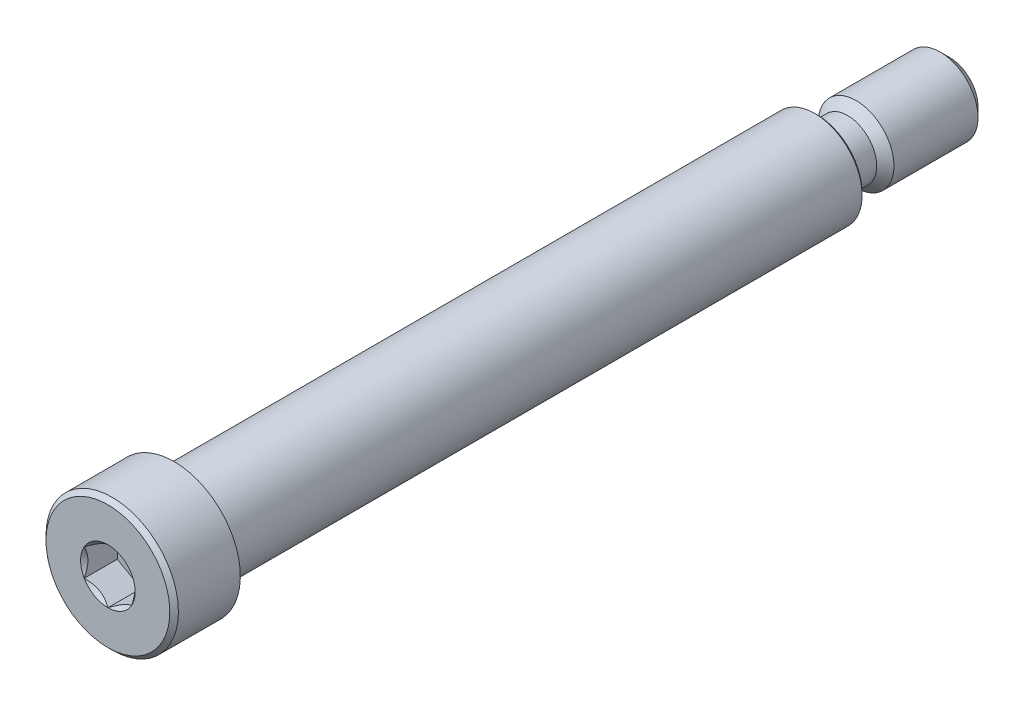
SolidWorks part; units mm, degrees
material "Cast Alloy Steel"
ref_plane "Front" through (0, 0, 0) normal (0, 0, 1) x (1, 0, 0)
ref_plane "Top" through (0, 0, 0) normal (0, 1, 0) x (1, 0, 0)
ref_plane "Right" through (0, 0, 0) normal (1, 0, 0) x (0, 0, -1)
sketch "Sketch1" plane through (0, 0, 0) normal (1, 0, 0) x (0, 0, -1)
  line L0 (0, 5.5562) -> (5.5562, 5.5562)
  line L1 (5.5562, 5.5562) -> (5.5562, 3.9687)
  line L2 (5.5562, 3.9687) -> (59.5313, 3.9687)
  line L3 (59.5313, 3.9687) -> (59.5312, 3.175)
  line L4 (59.5312, 3.175) -> (70.6438, 3.175)
  line L5 (70.6438, 3.175) -> (70.6437, 0)
  line L6 (70.6437, 0) -> (0, 0)
  line L7 (0, 0) -> (0, 5.5562)
  line L8 (0, 5.5562) -> (0, -5.5563) construction
  line L9 (70.6438, 3.175) -> (70.6437, -3.175) construction
  line L10 (59.5313, 3.9687) -> (59.5313, -3.9688) construction
  line L11 (70.6437, -3.175) -> (68.966, -3.175) construction
  line L12 (32.5437, 0) -> (32.5437, 3.9687) construction
  point P8 (68.7387, -3.175)
  point P12 (59.5312, 0)
  point P17 (10.9538, 3.9687)
  point P18 (32.5437, 0)
  point P19 (32.5437, 3.9687)
  point P20 (54.1337, 3.9687)
  point P21 (54.1337, -3.9688)
  point P22 (10.9538, -3.9688)
  dimension "Head Dia" = 11.1125
  dimension "Head Ht" = 5.5562
  dimension "Thread Lg" = 11.1125
  dimension "Thread Dia" = 6.35
  dimension "Shoulder Dia" = 7.9375
  dimension "Shoulder Lg" = 53.975
  dimension "D1" = 1.905
  dimension "D2" = 1.6778
  dimension "D3" = 26.9875
  dimension "D4" = 5.3975
revolve "Revolve1" add sketch "Sketch1" angle 360 mid plane about L6
ref_plane "Plane1" through (0, 0, -70.6437) normal (0, 0, 1) x (1, 0, 0)
sketch "Sketch3" [suppressed] plane through (0, 0, -70.6437) normal (0, 0, 1) x (1, 0, 0)
  circle A0 centre (0, 0) radius 3.175
sketch "Sketch5" plane through (0, 0, 0) normal (1, 0, 0) x (0, 0, -1)
  line L0 (59.5313, 3.9687) -> (63.5889, 3.9687)
  line L1 (63.5889, 3.9687) -> (62.0713, 2.4511)
  line L2 (62.0713, 2.4511) -> (60.2552, 2.4511)
  line L3 (59.5313, 3.9687) -> (59.5313, 3.175)
  line L5 (59.5312, 3.175) -> (70.6438, 3.175) construction
  line L6 (70.6437, 0) -> (62.0713, 0) construction
  line L7 (66.3575, 0) -> (66.3575, -3.175) construction
  arc A0 (59.5313, 3.175) -> (60.2552, 2.4511) centre (60.2552, 3.175) ccw
  dimension "D1" = 45
  dimension "CADB" = 2.54
  dimension "CADA" = 4.9022
revolve "Cut-Revolve1" cut sketch "Sketch5" angle 360 mid plane about L6
chamfer "Chamfer1" distance 0.7937 angle 45 1 edges at (0, 3.175, -70.6438)
chamfer "Chamfer2" distance 0.3612 angle 45 1 edges at (0, 5.5562, 0)
chamfer "Chamfer3" distance 0.2032 angle 45 1 edges at (0, 3.9687, -59.5313)
sketch "Sketch10" plane through (0, 0, 0) normal (1, 0, 0) x (0, 0, -1)
  line L0 (0.3612, 0) -> (5.1951, 0) construction
  line L1 (0.3612, -5.5562) -> (0.3612, 5.5562) construction
  line L3 (0.3612, 0) -> (0, 0) construction
  line L4 (5.1951, 0) -> (5.5562, 0) construction
  line L5 (5.5562, -5.5562) -> (5.5563, 5.5562) construction
  point P6 (2.7781, 0)
  dimension "D1" = 4.8339
ref_plane "Plane2" through (0, 0, -2.7781) normal (0, 0, 1) x (1, 0, 0)
sketch "Sketch11" plane through (0, 0, -2.7781) normal (0, 0, 1) x (1, 0, 0)
  line L0 (0, 5.2673) -> (0, 5.5562) construction
  line L1 (0, 5.2673) -> (0.1668, 5.5562)
  line L2 (0, 5.2673) -> (-0.1668, 5.5562)
  line L3 (-0.1668, 5.5562) -> (0.1668, 5.5562)
  line L4 (0, 0) -> (-0.1668, 5.5562) construction
  line L5 (0.1668, 5.5562) -> (0, 0) construction
  circle A1 centre (0, 0) radius 5.5562 construction
  circle A2 centre (0, 0) radius 5.2673 construction
  circle A3 centre (0, 0) radius 5.1951 construction
  point P3 (0, 0.0018)
  point P8 (2.3908, 0.7309)
  dimension "D1" = 0.2889
  dimension "D2" = 3.439
extrude "Cut-Extrude5" [suppressed] cut sketch "Sketch11" against normal mid plane 4.5922
pattern_circular "CirPattern1" [suppressed] count 99 over 360 of bodies 119
sketch "Sketch8" plane through (0, 0, 0) normal (0, 0, 1) x (1, 0, 0)
  line L1 (1.9844, 1.1457) -> (0, 2.2914)
  line L2 (0, 2.2914) -> (-1.9844, 1.1457)
  line L3 (-1.9844, 1.1457) -> (-1.9844, -1.1457)
  line L4 (-1.9844, -1.1457) -> (0, -2.2914)
  line L5 (0, -2.2914) -> (1.9844, -1.1457)
  line L6 (1.9844, -1.1457) -> (1.9844, 1.1457)
  circle A0 centre (0, 0) radius 1.9844 construction
  dimension "Hex" = 3.9688
extrude "Cut-Extrude2" cut sketch "Sketch8" against normal blind 2.7781
sketch "Sketch9" plane through (0, 0, 0) normal (0, 0, 1) x (1, 0, 0)
  circle A0 centre (0, 0) radius 2.2914
extrude "Cut-Extrude4" cut sketch "Sketch9" against normal blind 2.7781 draft 45
sketch "Front Sketch" plane through (0, 0, 0) normal (0, 0, 1) x (1, 0, 0)
  line L0 (1.9844, -1.1457) -> (1.9844, 1.1457) construction
  line L1 (-1.9844, 1.1457) -> (-1.9844, -1.1457) construction
  circle A0 centre (0, 0) radius 5.5562 construction
  point P4 (-1.9844, 0)
  point P5 (1.9844, 0)
  point P6 (5.5562, 0)
  point P9 (-5.5562, 0)
ref_plane "Contact Plane 1" [suppressed] through (0, 0, -5.5562) normal (0, 0, -1) x (-1, 0, 0)
ref_axis "Center Axis 1" [suppressed] through (0, 0, -70.6437) along (0, 0, 1)
curve "Helix/Spiral1" [suppressed] pitch 1.27 height 12.3825 turns 9.75
sketch "Sketch4" [suppressed] plane through (0, 0, 0) normal (1, 0, 0) x (0, 0, -1)
  line L0 (70.5644, 3.3125) -> (71.8344, 3.3125) construction
  line L1 (71.8344, 3.3125) -> (71.1994, 2.2126) construction
  line L3 (71.1994, 2.2126) -> (70.5644, 3.3125) construction
  line L4 (70.6041, 3.2437) -> (71.7947, 3.2437) construction
  line L5 (70.6438, 3.175) -> (71.755, 3.175) construction
  line L6 (71.12, 2.3501) -> (71.2788, 2.3501) construction
  line L7 (71.1994, 2.3501) -> (71.1994, 2.2126) construction
  line L8 (71.1994, 3.3125) -> (71.1994, 3.175) construction
  line L9 (70.6041, 3.2437) -> (71.7947, 3.2437)
  line L10 (71.7947, 3.2437) -> (71.2788, 2.3501)
  line L11 (71.2788, 2.3501) -> (71.12, 2.3501)
  line L12 (71.12, 2.3501) -> (70.6041, 3.2437)
  point P14 (71.1994, 3.2437)
  point P15 (71.1994, 3.3125)
  dimension "D1" = 1.27
  dimension "D2" = 0.1588
sweep "Cut-Sweep1" [suppressed] cut profiles "Sketch4" path "Helix/Spiral1"
sketch "Sketch12" [suppressed] plane through (0, 0, 0) normal (1, 0, 0) x (0, 0, -1)
  line L1 (59.5313, 3.7655) -> (59.3281, 3.9687)
  line L2 (59.3281, 3.9687) -> (5.5562, 3.9687)
  line L3 (5.5562, 3.9687) -> (5.5562, 0)
  line L4 (5.5562, -5.5562) -> (5.5563, 5.5562) construction
  line L5 (5.5562, 0) -> (59.5312, 0)
  line L6 (59.5313, 3.7655) -> (59.5313, 3.175)
  line L7 (62.0713, 2.4511) -> (60.2552, 2.4511) construction
  line L8 (62.0713, 2.4511) -> (60.2552, 2.4511)
  line L9 (62.0713, 2.4511) -> (62.0713, 0)
  line L10 (62.0713, 0) -> (59.5312, 0)
  arc A0 (59.5313, 3.175) -> (60.2552, 2.4511) centre (60.2552, 3.175) ccw construction
  arc A1 (59.5313, 3.175) -> (60.2552, 2.4511) centre (60.2552, 3.175) ccw
revolve "Revolve2" [suppressed] add sketch "Sketch12" angle 360 about L5
equation "\"D3@Helix/Spiral1\" = \"Thread Lg@Sketch1\" + \"D4@Helix/Spiral1\""
equation "\"D1@Chamfer1\" = \"Thread Dia@Sketch1\" * .125"
equation "\"D1@Cut-Extrude2\"= \"Head Ht@Sketch1\" * .5"
equation "\"D1@Cut-Extrude4\" = \"D1@Cut-Extrude2\""
equation "\"D1@Chamfer2\" = \"Head Dia@Sketch1\" * .0325"
equation "\"D1@Sketch1\"=\"D4@Helix/Spiral1\"*1.5"
equation "\"D1@Sketch11\"=\"D1@Chamfer2\"*.8"
equation "\"D1@Cut-Extrude5\"=\"D1@Sketch10\"*.95"
equation "\"D1@CirPattern1\"=(360/\"D2@Sketch11\")-6"
equation "\"D3@Sketch1\"=\"Shoulder Lg@Sketch1\"/2"
equation "\"D4@Sketch1\"=\"D3@Sketch1\"*.2"
equation "\"D1@Sketch4\"=\"D4@Helix/Spiral1\""
equation "\"D2@Sketch4\"=\"D1@Sketch4\"/8"
